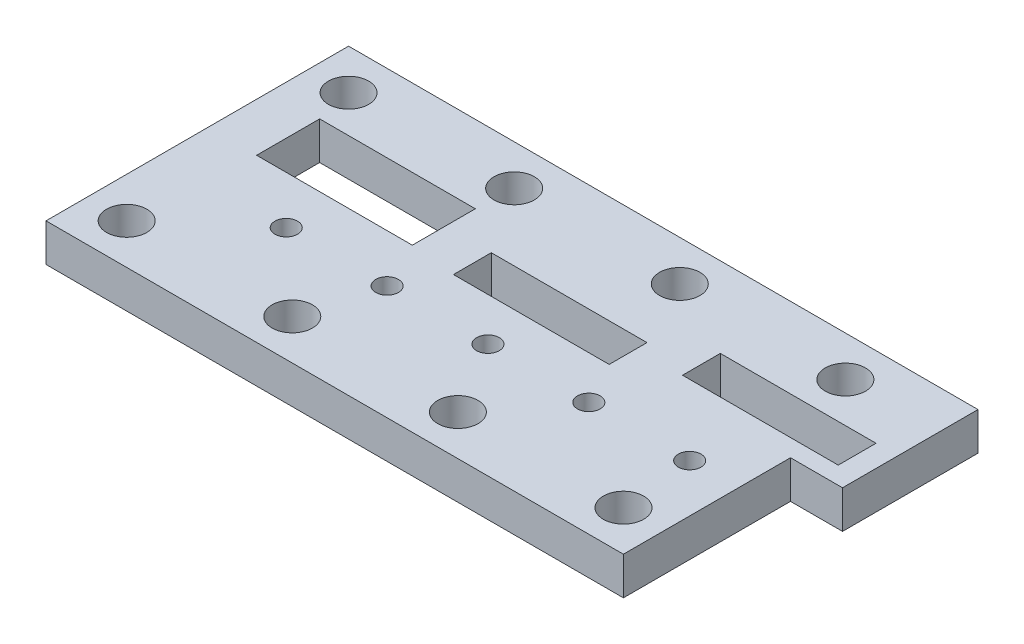
SolidWorks part; units mm, degrees
material "Plain Carbon Steel"
ref_plane "Front Plane" through (0, 0, 0) normal (0, 0, 1) x (1, 0, 0)
ref_plane "Top Plane" through (0, 0, 0) normal (0, 1, 0) x (1, 0, 0)
ref_plane "Right Plane" through (0, 0, 0) normal (1, 0, 0) x (0, 0, -1)
sketch "Sketch1" plane through (0, 0, 0) normal (0, 1, 0) x (1, 0, 0)
  line L0 (-229, 60) -> (-229, -60) construction
  line L1 (-229, -60) -> (0, -60)
  line L2 (-229, -60) -> (-229, 60)
  line L3 (-229, 60) -> (0, 60)
  line L4 (0, -60) -> (0, 60)
  point P4 (0, 0)
  dimension "D1" = 120
extrude "Boss-Extrude1" add sketch "Sketch1" along normal mid plane 15
ref_plane "Plane2" through (-114.5, 0, 0) normal (1, 0, 0) x (0, 0, -1)
sketch "Sketch4" plane through (0, 7.5, 0) normal (0, 1, 0) x (1, 0, 0)
  line L1 (0, 60) -> (20.6325, 60)
  line L2 (0, 60) -> (0, 6.27)
  line L3 (0, 6.27) -> (20.6325, 6.27)
  line L4 (20.6325, 60) -> (20.6325, 6.27)
extrude "Boss-Extrude2" add sketch "Sketch4" against normal up to surface (15 mm away) up to face at (-114.5, -7.5, 0)
sketch "Sketch5" plane through (0, 7.5, 0) normal (0, 1, 0) x (1, 0, 0)
  line L1 (-129.75, 17.3524) -> (-68, 17.3524)
  line L2 (-129.75, 17.3524) -> (-129.75, 2.3524)
  line L3 (-129.75, 2.3524) -> (-68, 2.3524)
  line L4 (-68, 17.3524) -> (-68, 2.3524)
  line L5 (-49.75, 28.191) -> (12, 28.191)
  line L6 (-49.75, 28.191) -> (-49.75, 13.191)
  line L7 (-49.75, 13.191) -> (12, 13.191)
  line L8 (12, 28.191) -> (12, 13.191)
  line L9 (-209.75, 29.28) -> (-148, 29.28)
  line L10 (-209.75, 29.28) -> (-209.75, 4.28)
  line L11 (-209.75, 4.28) -> (-148, 4.28)
  line L12 (-148, 29.28) -> (-148, 4.28)
extrude "Cut-Extrude1" cut sketch "Sketch5" against normal up to next
sketch "Sketch8" plane through (0, 7.5, 0) normal (0, 1, 0) x (1, 0, 0)
  line L3 (-11, 0) -> (11, 0) construction
  line L4 (-114.5, -11) -> (-114.5, 11) construction
  circle A0 centre (-213, 44) radius 8
  dimension "D1" = 16
  dimension "D2" = 44
  dimension "D3" = 98.5
extrude "Cut-Extrude4" cut sketch "Sketch8" against normal up to next
pattern_linear "LPattern2" count 4 spacing 65.677 along (1, 0, 0) count 2 spacing 88 along (0, 0, 1) of "Cut-Extrude4"
hole_wizard "Ø9.0 (9) Diameter Hole1" positions "Sketch11" profile "Sketch10" hole size "Ø9.0" standard "ISO" end condition through all
sketch "Sketch11" plane through (0, 7.5, 0) normal (0, 1, 0) x (1, 0, 0)
  point P0 (-179, -14.72)
  point P3 (-139, -14.72)
  point P6 (-99, -14.72)
  point P9 (-59, -14.72)
  point P12 (-19, -14.72)
sketch "Sketch10" plane through (-179, 7.5, 14.72) normal (1, 0, 0) x (0, 0, 1)
  line L0 (0, 0) -> (0, 15)
  line L1 (0, 15) -> (4.5, 15)
  line L2 (4.5, 15) -> (4.5, 0)
  line L5 (4.5, 0) -> (0, 0)
  line L11 (0, -6.35) -> (0, 107.95) construction
  dimension "Thru Hole Dia." = 9
  dimension "Thru Hole Depth" = 15
